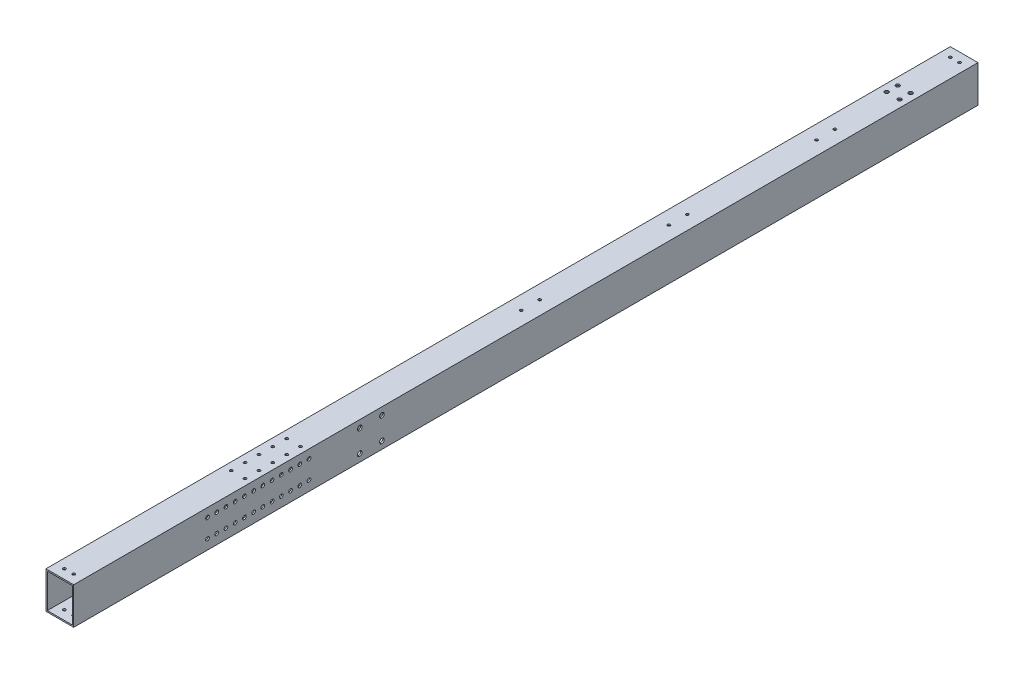
SolidWorks part; units mm, degrees
ref_plane "前视基准面" through (0, 0, 0) normal (0, 0, 1) x (1, 0, 0)
ref_plane "上视基准面" through (0, 0, 0) normal (0, 1, 0) x (1, 0, 0)
ref_plane "右视基准面" through (0, 0, 0) normal (1, 0, 0) x (0, 0, -1)
sketch "草图1" plane through (0, 0, 0) normal (0, 0, 1) x (1, 0, 0)
  line L0 (-13.5, 18.5) -> (13.5, 18.5)
  line L1 (-15, -20) -> (15, -20)
  line L2 (-15, -20) -> (-15, 20)
  line L3 (-15, 20) -> (15, 20)
  line L4 (15, -20) -> (15, 20)
  line L5 (-15, -20) -> (15, 20) construction
  line L6 (-15, 20) -> (15, -20) construction
  line L7 (13.5, -18.5) -> (13.5, 18.5)
  line L8 (-13.5, -18.5) -> (13.5, -18.5)
  line L9 (-13.5, -18.5) -> (-13.5, 18.5)
  point P0 (0, 0)
  dimension "D1" = 40
  dimension "D2" = 30
  dimension "D3" = 1.5
extrude "凸台-拉伸1" add sketch "草图1" along normal blind 980
sketch "草图2" plane through (0, 20, 0) normal (0, -1, 0) x (-1, 0, 0)
  line L0 (0, 0) -> (0, -50000) construction
  circle A0 centre (11, -65) radius 1.5
  circle A1 centre (-11, -65) radius 1.5
  circle A2 centre (11, -515) radius 1.5
  circle A3 centre (-11, -515) radius 1.5
  circle A4 centre (11, -105) radius 1.5
  circle A5 centre (-11, -105) radius 1.5
  dimension "D1" = 3
  dimension "D4" = 3
  dimension "D7" = 3
  dimension "D2" = 22
  dimension "D3" = 65
  dimension "D6" = 450
  dimension "D8" = 40
extrude "切除-拉伸1" [suppressed] cut sketch "草图2" along normal blind 1040
sketch "草图3" plane through (0, 20, 0) normal (0, -1, 0) x (-1, 0, 0)
  line L0 (0, 0) -> (0, -50000) construction
  line L2 (-16.5, -490) -> (49983.5, -490) construction
  line L3 (13.5, 0) -> (13.5, -980) construction
  line L4 (-13.5, 0) -> (-13.5, -980) construction
  line L5 (-15, 0) -> (15, 0) construction
  circle A0 centre (5, -10) radius 1.5
  circle A1 centre (-5, -10) radius 1.5
  circle A2 centre (-5, -970) radius 1.5
  circle A3 centre (5, -970) radius 1.5
  point P13 (13.5, -490)
  point P16 (-13.5, -490)
  dimension "D1" = 3
  dimension "D2" = 10
  dimension "D3" = 10
extrude "切除-拉伸2" cut sketch "草图3" along normal through all
sketch "草图4" plane through (0, 20, 0) normal (0, -1, 0) x (-1, 0, 0)
  line L1 (-8.2701, -787.5) -> (6.7299, -787.5) construction
  line L2 (-8.2701, -787.5) -> (-8.2701, -772.5) construction
  line L3 (-8.2701, -772.5) -> (6.7299, -772.5) construction
  line L4 (6.7299, -787.5) -> (6.7299, -772.5) construction
  line L5 (-8.2701, -787.5) -> (6.7299, -772.5) construction
  line L6 (-8.2701, -772.5) -> (6.7299, -787.5) construction
  line L7 (-0.7701, -780) -> (49999.2299, -780) construction
  line L8 (-0.7701, -840) -> (-0.7701, -50840) construction
  line L9 (15, -980) -> (-15, -980) construction
  circle A0 centre (-8.2701, -772.5) radius 1.5
  circle A1 centre (6.7299, -772.5) radius 1.5
  circle A2 centre (6.7299, -787.5) radius 1.5
  circle A3 centre (-8.2701, -787.5) radius 1.5
  point P0 (-0.7701, -780)
  dimension "D4" = 3
  dimension "D1" = 15
  dimension "D2" = 15
  dimension "D3" = 200
extrude "切除-拉伸3" cut sketch "草图4" along normal through all
sketch "草图5" plane through (0, 20, 0) normal (0, -1, 0) x (-1, 0, 0)
  line L0 (0, 0) -> (0, -50000) construction
  line L2 (0, -140) -> (0, -300) construction
  line L3 (0, -320) -> (0, -480) construction
  line L4 (15, 0) -> (-15, 0) construction
  circle A0 centre (0, -140) radius 1.5
  circle A1 centre (0, -160) radius 1.5
  circle A2 centre (0, -300) radius 1.5
  circle A3 centre (0, -320) radius 1.5
  circle A4 centre (0, -480) radius 1.5
  circle A5 centre (0, -460) radius 1.5
  dimension "D1" = 3
  dimension "D2" = 3
  dimension "D3" = 20
  dimension "D4" = 140
  dimension "D6" = 160
  dimension "D8" = 160
  dimension "D5" = 2
  dimension "D7" = 2
extrude "切除-拉伸4" cut sketch "草图5" along normal through all
sketch "草图8" plane through (0, -20, 0) normal (0, -1, 0) x (1, 0, 0)
  line L0 (0, 160) -> (0, 140) construction
  line L1 (7.5, 160) -> (7.5, 140)
  line L2 (-7.5, 160) -> (-7.5, 140)
  line L3 (0, 480) -> (0, 460) construction
  line L4 (7.5, 480) -> (7.5, 460)
  line L5 (-7.5, 480) -> (-7.5, 460)
  line L6 (0, 320) -> (0, 300) construction
  line L7 (7.5, 320) -> (7.5, 300)
  line L8 (-7.5, 320) -> (-7.5, 300)
  arc A0 (7.5, 160) -> (-7.5, 160) centre (0, 160) ccw
  arc A1 (-7.5, 140) -> (7.5, 140) centre (0, 140) ccw
  arc A2 (7.5, 480) -> (-7.5, 480) centre (0, 480) ccw
  arc A3 (-7.5, 460) -> (7.5, 460) centre (0, 460) ccw
  arc A4 (7.5, 320) -> (-7.5, 320) centre (0, 320) ccw
  arc A5 (-7.5, 300) -> (7.5, 300) centre (0, 300) ccw
  point P4 (0, 150)
  point P13 (0, 470)
  point P18 (0, 310)
  dimension "D1" = 7.5
  dimension "D2" = 7.5
  dimension "D3" = 7.5
extrude "切除-拉伸6" cut sketch "草图8" against normal blind 10
sketch "草图9" plane through (0, -20, 0) normal (0, -1, 0) x (1, 0, 0)
  circle A0 centre (-6.7299, 787.5) radius 3.25
  circle A1 centre (-6.7299, 772.5) radius 3.25
  circle A2 centre (8.2701, 772.5) radius 3.25
  circle A3 centre (8.2701, 787.5) radius 3.25
  dimension "D1" = 6.5
  dimension "D2" = 6.5
  dimension "D3" = 6.5
  dimension "D4" = 6.5
extrude "切除-拉伸7" cut sketch "草图9" against normal blind 10
pattern_linear "阵列(线性)1" count 4 spacing 15 along (0, 0, -1) of "切除-拉伸3", "切除-拉伸7"
sketch "草图10" plane through (-15, 0, 0) normal (-1, 0, 0) x (0, 0, 1)
  line L1 (0, 0) -> (664.4549, 0) construction
  line L2 (980, 20) -> (980, -20) construction
  circle A0 centre (646, 12) radius 2.55
  circle A1 centre (670, 12) radius 2.55
  circle A2 centre (646, -12) radius 2.55
  circle A3 centre (670, -12) radius 2.55
  dimension "D1" = 310
  dimension "D2" = 5.1
  dimension "D5" = 24
  dimension "D6" = 12
  dimension "D3" = 2
  dimension "D4" = 2
extrude "切除-拉伸8" cut sketch "草图10" against normal blind 51
sketch "草图11" plane through (-15, 0, 0) normal (-1, 0, 0) x (0, 0, 1)
  line L1 (980, 20) -> (980, -20) construction
  circle A0 centre (725, 10.6252) radius 2
  circle A1 centre (725, -9.3748) radius 2
  circle A2 centre (735, 10.6252) radius 2
  circle A3 centre (735, -9.3748) radius 2
  circle A4 centre (745, 10.6252) radius 2
  circle A5 centre (745, -9.3748) radius 2
  circle A6 centre (755, 10.6252) radius 2
  circle A7 centre (755, -9.3748) radius 2
  circle A8 centre (765, 10.6252) radius 2
  circle A9 centre (765, -9.3748) radius 2
  circle A10 centre (775, 10.6252) radius 2
  circle A11 centre (775, -9.3748) radius 2
  circle A12 centre (785, 10.6252) radius 2
  circle A13 centre (785, -9.3748) radius 2
  circle A14 centre (795, 10.6252) radius 2
  circle A15 centre (795, -9.3748) radius 2
  circle A16 centre (805, 10.6252) radius 2
  circle A17 centre (805, -9.3748) radius 2
  circle A18 centre (815, 10.6252) radius 2
  circle A19 centre (815, -9.3748) radius 2
  circle A20 centre (825, 10.6252) radius 2
  circle A21 centre (825, -9.3748) radius 2
  circle A22 centre (835, 10.6252) radius 2
  circle A23 centre (835, -9.3748) radius 2
  dimension "D1" = 4
  dimension "D2" = 2
  dimension "D4" = 145
  dimension "D3" = 12
extrude "切除-拉伸9" cut sketch "草图11" against normal blind 51
sketch "草图12" plane through (0, 20, 0) normal (0, 1, 0) x (1, 0, 0)
  line L0 (0, 0) -> (0, -98.6612) construction
  line L1 (15, 0) -> (-15, 0) construction
  circle A0 centre (-7, -65) radius 2.1
  circle A1 centre (-7, -77) radius 2.1
  circle A2 centre (7, -77) radius 2.1
  circle A3 centre (7, -65) radius 2.1
  dimension "D1" = 65
  dimension "D2" = 4.2
  dimension "D4" = 14
  dimension "D3" = 2
extrude "切除-拉伸10" cut sketch "草图12" against normal blind 10
sketch "草图13" plane through (0, -20, 0) normal (0, -1, 0) x (1, 0, 0)
  line L0 (0, 70.1408) -> (0, 99.7127) construction
  line L1 (-8.2089, 70.1408) -> (-8.2089, 99.7127)
  line L2 (8.2089, 70.1408) -> (8.2089, 99.7127)
  arc A0 (-8.2089, 70.1408) -> (8.2089, 70.1408) centre (0, 70.1408) ccw
  arc A1 (8.2089, 99.7127) -> (-8.2089, 99.7127) centre (0, 99.7127) ccw
  point P3 (0, 84.9268)
extrude "切除-拉伸11" cut sketch "草图13" against normal blind 10
equation "\"5。7\"=6"
